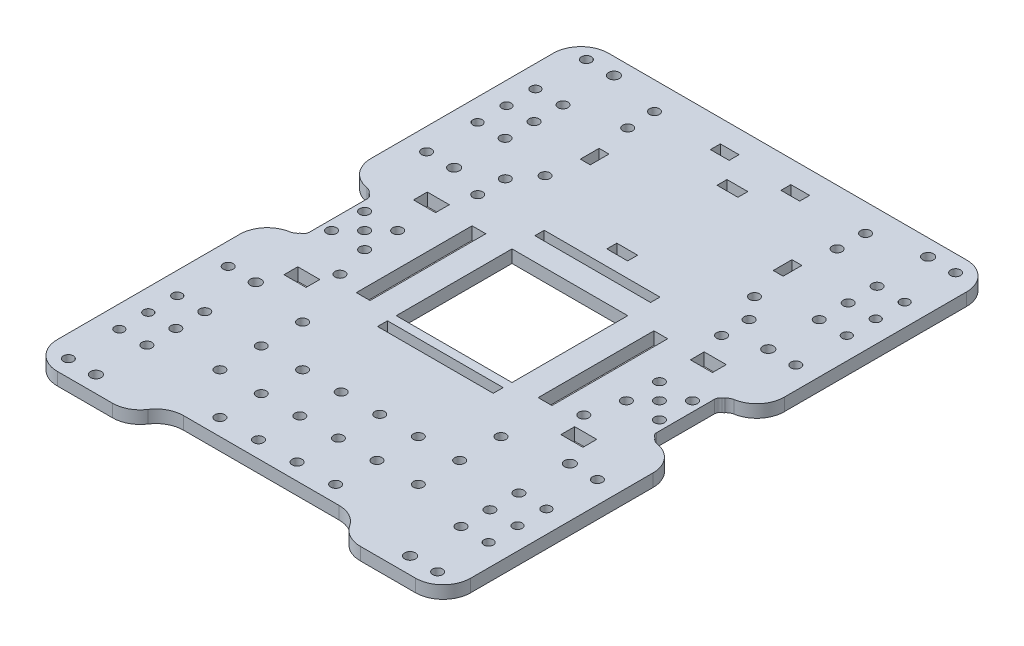
SolidWorks part; units mm, degrees
ref_plane "前视基准面" through (0, 0, 0) normal (0, 0, 1) x (1, 0, 0)
ref_plane "上视基准面" through (0, 0, 0) normal (0, 1, 0) x (1, 0, 0)
ref_plane "右视基准面" through (0, 0, 0) normal (1, 0, 0) x (0, 0, -1)
other "Configuration Table"
sketch "草图2" plane through (0, 0, 0) normal (0, 1, 0) x (1, 0, 0)
  line L0 (-65, 0) -> (65, 0) construction
  line L1 (-65, 100) -> (65, 100)
  line L2 (-65, 100) -> (-65, -100)
  line L3 (-65, -100) -> (65, -100)
  line L4 (65, 100) -> (65, -100)
  line L5 (-65, 100) -> (65, -100) construction
  line L6 (-65, -100) -> (65, 100) construction
  line L7 (65, 0) -> (63, 0) construction
  line L8 (63, 0) -> (59.5, 0) construction
  line L9 (59.5, 0) -> (47.5, 0) construction
  line L10 (47.5, 0) -> (53.5, 0) construction
  line L11 (53.5, 0) -> (53.5, 6) construction
  line L12 (53.5, 6) -> (53.5, -6) construction
  line L13 (53.5, -6) -> (47.5, -6) construction
  line L14 (47.5, -6) -> (47.5, 6) construction
  line L15 (47.5, 6) -> (59.5, 6) construction
  line L16 (59.5, 6) -> (59.5, -6) construction
  line L17 (-65, 0) -> (-63, 0) construction
  line L18 (-63, 0) -> (-59.5, 0) construction
  line L19 (-59.5, 0) -> (-47.5, 0) construction
  line L20 (-47.5, 0) -> (-53.5, 0) construction
  line L21 (-53.5, 0) -> (-53.5, 6) construction
  line L22 (-53.5, 6) -> (-53.5, -6) construction
  line L23 (-53.5, -6) -> (-59.5, -6) construction
  line L24 (-59.5, -6) -> (-59.5, 6) construction
  line L25 (-59.5, 6) -> (-47.5, 6) construction
  line L26 (-47.5, 6) -> (-47.5, -6) construction
  circle A0 centre (-59.5, 6) radius 1.8
  circle A1 centre (-47.5, 6) radius 1.8
  circle A2 centre (-59.5, -6) radius 1.8
  circle A3 centre (-47.5, -6) radius 1.8
  circle A4 centre (-53.5, 0) radius 1.8
  circle A5 centre (53.5, 0) radius 1.8
  circle A6 centre (59.5, 6) radius 1.8
  circle A7 centre (59.5, -6) radius 1.8
  circle A8 centre (47.5, -6) radius 1.8
  circle A9 centre (47.5, 6) radius 1.8
  point P0 (0, 0)
  dimension "D13" = 3.6
  dimension "D14" = 3.6
  dimension "D15" = 3.6
  dimension "D16" = 3.6
  dimension "D17" = 3.6
  dimension "D18" = 3.6
  dimension "D19" = 3.6
  dimension "D20" = 3.6
  dimension "D21" = 3.6
  dimension "D22" = 3.6
  dimension "D1" = 200
  dimension "D2" = 130
  dimension "D3" = 2
  dimension "D4" = 3.5
  dimension "D5" = 12
  dimension "D6" = 6
  dimension "D7" = 12
  dimension "D8" = 2
  dimension "D9" = 3.5
  dimension "D10" = 12
  dimension "D11" = 6
  dimension "D12" = 12
extrude "凸台-拉伸1" add sketch "草图2" along normal blind 4.6
fillet "圆角1" radius 5 4 edges at (-65, 2.3, -100) (65, 2.3, -100) (-65, 2.3, 100) (65, 2.3, 100)
sketch "草图3" plane through (0, 4.6, 0) normal (0, 1, 0) x (1, 0, 0)
  line L0 (-65, 0) -> (65, 0) construction
  line L1 (-65, 95) -> (-65, -95) construction
  line L2 (65, -95) -> (65, 95) construction
  line L4 (-63, 12) -> (-67, 12)
  line L5 (-63, 12) -> (-63, -12)
  line L6 (-63, -12) -> (-67, -12)
  line L7 (-67, 12) -> (-67, -12)
  line L8 (-63, 12) -> (-67, -12) construction
  line L9 (-63, -12) -> (-67, 12) construction
  line L10 (63, 12) -> (67, 12)
  line L11 (63, 12) -> (63, -12)
  line L12 (63, -12) -> (67, -12)
  line L13 (67, 12) -> (67, -12)
  line L14 (63, 12) -> (67, -12) construction
  line L15 (63, -12) -> (67, 12) construction
  dimension "D1" = 24
  dimension "D2" = 4
  dimension "D3" = 24
  dimension "D4" = 4
extrude "切除-拉伸1" cut sketch "草图3" against normal blind 4.6
fillet "圆角2" radius 2 4 edges at (65, 2.3, 12) (65, 2.3, -12) (-65, 2.3, 12) (-65, 2.3, -12)
fillet "圆角3" radius 2 4 edges at (-63, 2.3, 12) (-63, 2.3, -12) (63, 2.3, 12) (63, 2.3, -12)
sketch "草图4" plane through (0, 0, 0) normal (0, 1, 0) x (1, 0, 0)
  line L0 (65, 14) -> (57, 14) construction
  line L1 (57, 14) -> (57, 120) construction
  line L2 (65, -14) -> (57, -14) construction
  line L3 (65, -95) -> (65, -14) construction
  line L4 (57, -14) -> (57, -94) construction
  line L5 (57, -94) -> (57, -65) construction
  line L6 (57, -65) -> (57, -54) construction
  line L7 (-65, -94) -> (-57, -94) construction
  line L8 (-65, -14) -> (-65, -95) construction
  line L9 (-57, -94) -> (-57, -65) construction
  line L10 (-57, -65) -> (-57, -54.5) construction
  line L11 (-57, -54.5) -> (-57, -65) construction
  line L12 (-57, -65) -> (-57, -36) construction
  line L13 (57, -65) -> (57, -36) construction
  line L14 (57, 14) -> (57, 36) construction
  line L15 (57, 36) -> (57, 65) construction
  line L16 (57, 65) -> (57, 75.5) construction
  line L17 (57, 75.5) -> (57, 54.5) construction
  line L18 (57, 65) -> (57, 94) construction
  line L19 (-65, 14) -> (-57, 14) construction
  line L20 (-57, 14) -> (-57, 36) construction
  line L21 (-57, 36) -> (-57, 54.5) construction
  line L22 (-57, 54.5) -> (-57, 65) construction
  line L23 (-57, 65) -> (-57, 75.5) construction
  line L24 (-57, 75.5) -> (-57, 94) construction
  line L25 (-57, -65) -> (-57, -75.5) construction
  line L26 (-57, -75.5) -> (57, -75.5) construction
  line L27 (57, -65) -> (57, -54.5) construction
  arc A0 (65, -14) -> (64, -12.2679) centre (63, -14) ccw construction
  circle A1 centre (57, 65) radius 1.8
  circle A2 centre (57, 75.5) radius 1.8
  circle A3 centre (57, 54.5) radius 1.8
  circle A4 centre (57, 94) radius 1.95
  circle A5 centre (57, 36) radius 1.95
  circle A6 centre (-57, 94) radius 1.95
  circle A7 centre (-57, 75.5) radius 1.8
  circle A8 centre (-57, 65) radius 1.8
  circle A9 centre (-57, 54.5) radius 1.8
  circle A10 centre (-57, 36) radius 1.95
  circle A11 centre (-57, -36) radius 1.95
  circle A12 centre (-57, -65) radius 1.8
  circle A13 centre (-57, -54.5) radius 1.8
  circle A14 centre (-57, -75.5) radius 1.8
  circle A15 centre (-57, -94) radius 1.95
  circle A16 centre (57, -65) radius 1.8
  circle A18 centre (57, -75.5) radius 1.8
  circle A19 centre (57, -54.5) radius 1.8
  circle A20 centre (57, -36) radius 1.95
  circle A21 centre (57, -94) radius 1.95
  dimension "D15" = 3.6
  dimension "D16" = 3.6
  dimension "D17" = 3.6
  dimension "D18" = 3.9
  dimension "D19" = 3.9
  dimension "D20" = 3.9
  dimension "D21" = 3.6
  dimension "D22" = 3.6
  dimension "D23" = 3.6
  dimension "D24" = 3.9
  dimension "D25" = 3.9
  dimension "D26" = 3.6
  dimension "D27" = 3.6
  dimension "D29" = 3.6
  dimension "D30" = 3.9
  dimension "D31" = 3.6
  dimension "D32" = 10.5
  dimension "D33" = 3.6
  dimension "D34" = 3.6
  dimension "D35" = 3.9
  dimension "D36" = 3.9
  dimension "D1" = 8
  dimension "D2" = 106
  dimension "D3" = 8
  dimension "D4" = 80
  dimension "D5" = 29
  dimension "D6" = 11
  dimension "D7" = 8
  dimension "D8" = 29
  dimension "D9" = 22
  dimension "D10" = 29
  dimension "D11" = 10.5
  dimension "D12" = 21
  dimension "D13" = 29
  dimension "D14" = 8
  dimension "D28" = 10.5
extrude "切除-拉伸2" cut sketch "草图4" along normal blind 4.6
sketch "草图5" plane through (0, 4.6, 0) normal (0, 1, 0) x (1, 0, 0)
  line L0 (0, 100) -> (38.3, 100) construction
  line L1 (60, 100) -> (-60, 100) construction
  line L2 (38.3, 100) -> (-38.3, 100) construction
  line L3 (-38.3, 100) -> (-38.3, 90) construction
  line L4 (-38.3, 90) -> (-12.8, 90) construction
  line L5 (38.3, 100) -> (38.3, 90) construction
  line L6 (38.3, 90) -> (12.8, 90) construction
  line L7 (0, 21) -> (0, 31) construction
  line L8 (-16.2, 91.8) -> (-9.4, 91.8)
  line L9 (-16.2, 91.8) -> (-16.2, 88.2)
  line L10 (-16.2, 88.2) -> (-9.4, 88.2)
  line L11 (-9.4, 91.8) -> (-9.4, 88.2)
  line L12 (-16.2, 91.8) -> (-9.4, 88.2) construction
  line L13 (-16.2, 88.2) -> (-9.4, 91.8) construction
  line L14 (9.4, 91.8) -> (16.2, 91.8)
  line L15 (9.4, 91.8) -> (9.4, 88.2)
  line L16 (9.4, 88.2) -> (16.2, 88.2)
  line L17 (16.2, 91.8) -> (16.2, 88.2)
  line L18 (9.4, 91.8) -> (16.2, 88.2) construction
  line L19 (9.4, 88.2) -> (16.2, 91.8) construction
  line L20 (-21, 21) -> (21, 21)
  line L21 (-21, 21) -> (-21, -21)
  line L22 (-21, -21) -> (21, -21)
  line L23 (21, 21) -> (21, -21)
  line L24 (-21, 21) -> (21, -21) construction
  line L25 (-21, -21) -> (21, 21) construction
  line L26 (0, 31) -> (0, -21) construction
  line L27 (0, -21) -> (0, -31) construction
  line L28 (-60, -100) -> (60, -100) construction
  line L29 (-21, 32.7) -> (21, 32.7)
  line L30 (-21, 32.7) -> (-21, 29.3)
  line L31 (-21, 29.3) -> (21, 29.3)
  line L32 (21, 32.7) -> (21, 29.3)
  line L33 (-21, 32.7) -> (21, 29.3) construction
  line L34 (-21, 29.3) -> (21, 32.7) construction
  line L35 (-21, -29.3) -> (21, -29.3)
  line L36 (-21, -29.3) -> (-21, -32.7)
  line L37 (-21, -32.7) -> (21, -32.7)
  line L38 (21, -29.3) -> (21, -32.7)
  line L39 (-21, -29.3) -> (21, -32.7) construction
  line L40 (-21, -32.7) -> (21, -29.3) construction
  line L41 (-35, -91) -> (35, -91)
  line L42 (-35, -91) -> (-35, -109)
  line L43 (-35, -109) -> (35, -109)
  line L44 (35, -91) -> (35, -109)
  line L45 (-35, -91) -> (35, -109) construction
  line L46 (-35, -109) -> (35, -91) construction
  circle A0 centre (38.3, 90) radius 1.8
  circle A1 centre (-38.3, 90) radius 1.8
  point P19 (0, 0)
  point P37 (0, -100)
  dimension "D7" = 3.6
  dimension "D8" = 3.6
  dimension "D1" = 38.3
  dimension "D2" = 76.6
  dimension "D3" = 10
  dimension "D4" = 25.5
  dimension "D5" = 10
  dimension "D6" = 25.5
  dimension "D9" = 3.6
  dimension "D10" = 6.8
  dimension "D11" = 3.6
  dimension "D12" = 6.8
  dimension "D13" = 42
  dimension "D14" = 10
  dimension "D15" = 10
  dimension "D16" = 3.4
  dimension "D17" = 42
  dimension "D18" = 3.4
  dimension "D19" = 42
  dimension "D20" = 18
  dimension "D21" = 70
extrude "切除-拉伸3" cut sketch "草图5" against normal blind 4.6
fillet "圆角4" radius 10 2 edges at (-35, 2.3, 100) (35, 2.3, 100)
fillet "圆角5" radius 10 2 edges at (-35, 2.3, 91) (35, 2.3, 91)
sketch "草图6" plane through (0, 4.6, 0) normal (0, 1, 0) x (1, 0, 0)
  line L0 (0, -91) -> (0, -85) construction
  line L1 (28.2466, -91) -> (-28.2466, -91) construction
  line L2 (0, -85) -> (-7, -85) construction
  line L3 (-7, -85) -> (7, -85) construction
  line L4 (7, -85) -> (21, -85) construction
  line L5 (21, -85) -> (21, -70) construction
  line L6 (21, -70) -> (21, -55) construction
  line L7 (21, -55) -> (7, -55) construction
  line L8 (7, -55) -> (-7, -55) construction
  line L9 (-7, -55) -> (-21, -55) construction
  line L10 (-21, -55) -> (-35, -55) construction
  line L11 (-35, -55) -> (-35, -70) construction
  line L12 (-35, -70) -> (-35, -85) construction
  line L13 (-35, -85) -> (-21, -85) construction
  line L14 (21, -85) -> (35, -85) construction
  line L15 (35, -85) -> (35, -70) construction
  line L16 (35, -70) -> (35, -55) construction
  line L17 (35, -55) -> (35, -40) construction
  line L18 (35, -40) -> (21, -40) construction
  line L19 (21, -40) -> (7, -40) construction
  line L20 (7, -40) -> (-7, -40) construction
  line L21 (-7, -40) -> (-21, -40) construction
  line L22 (-21, -40) -> (-35, -40) construction
  line L23 (-35, -40) -> (-35, -70) construction
  line L24 (-35, -70) -> (-21, -70) construction
  line L25 (-21, -70) -> (-7, -70) construction
  line L26 (-7, -70) -> (7, -70) construction
  line L27 (21, -70) -> (36, -70) construction
  line L28 (36, -70) -> (36, -55) construction
  line L29 (36, -55) -> (36, -40) construction
  line L30 (-21, -70) -> (-36, -70) construction
  line L31 (-36, -70) -> (-36, -55) construction
  line L32 (-36, -55) -> (-36, -40) construction
  circle A0 centre (-7, -85) radius 1.8
  circle A1 centre (-21, -85) radius 1.8
  circle A2 centre (7, -85) radius 1.8
  circle A3 centre (21, -85) radius 1.8
  circle A4 centre (21, -70) radius 1.8
  circle A5 centre (7, -70) radius 1.8
  circle A6 centre (-7, -70) radius 1.8
  circle A7 centre (-21, -70) radius 1.8
  circle A8 centre (-21, -55) radius 1.8
  circle A9 centre (-7, -55) radius 1.8
  circle A10 centre (7, -55) radius 1.8
  circle A11 centre (21, -55) radius 1.8
  circle A12 centre (36, -70) radius 1.8
  circle A13 centre (36, -55) radius 1.8
  circle A14 centre (36, -40) radius 1.8
  circle A15 centre (-36, -40) radius 1.8
  circle A16 centre (-36, -55) radius 1.8
  circle A17 centre (-36, -70) radius 1.8
  dimension "D15" = 3.6
  dimension "D16" = 3.6
  dimension "D17" = 3.6
  dimension "D18" = 3.6
  dimension "D19" = 3.6
  dimension "D20" = 3.6
  dimension "D21" = 3.6
  dimension "D22" = 3.6
  dimension "D23" = 3.6
  dimension "D24" = 3.6
  dimension "D25" = 3.6
  dimension "D26" = 3.6
  dimension "D27" = 15
  dimension "D33" = 3.6
  dimension "D34" = 3.6
  dimension "D35" = 3.6
  dimension "D36" = 3.6
  dimension "D37" = 3.6
  dimension "D38" = 3.6
  dimension "D1" = 6
  dimension "D2" = 7
  dimension "D3" = 14
  dimension "D4" = 14
  dimension "D5" = 15
  dimension "D6" = 15
  dimension "D7" = 14
  dimension "D8" = 14
  dimension "D9" = 14
  dimension "D10" = 14
  dimension "D11" = 15
  dimension "D12" = 14
  dimension "D13" = 14
  dimension "D14" = 15
  dimension "D28" = 15
  dimension "D29" = 15
  dimension "D30" = 15
  dimension "D31" = 15
  dimension "D32" = 15
extrude "切除-拉伸4" cut sketch "草图6" against normal blind 4.6
sketch "草图7" plane through (0, 4.6, 0) normal (0, 1, 0) x (1, 0, 0)
  line L0 (0, 100) -> (38, 100) construction
  line L1 (60, 100) -> (-60, 100) construction
  line L2 (38, 100) -> (-38, 100) construction
  line L3 (-38, 100) -> (-38, 80) construction
  line L4 (-38, 80) -> (-38, 50) construction
  line L5 (-38, 50) -> (38, 50) construction
  line L6 (38, 50) -> (38, 80) construction
  circle A0 centre (-38, 80) radius 1.8
  circle A1 centre (38, 80) radius 1.8
  circle A2 centre (38, 50) radius 1.8
  circle A3 centre (-38, 50) radius 1.8
  dimension "D7" = 3.6
  dimension "D8" = 3.6
  dimension "D9" = 3.6
  dimension "D10" = 3.6
  dimension "D1" = 38
  dimension "D2" = 76
  dimension "D3" = 20
  dimension "D4" = 30
  dimension "D5" = 76
  dimension "D6" = 30
extrude "切除-拉伸5" cut sketch "草图7" against normal blind 4.6
sketch "草图8" plane through (0, 4.6, 0) normal (0, 1, 0) x (1, 0, 0)
  line L0 (-38, 80) -> (38, 50) construction
  line L1 (38, 50) -> (0, 65) construction
  line L2 (0, 65) -> (-35, 65) construction
  line L3 (-35, 65) -> (35, 65) construction
  line L4 (35, 65) -> (0, 65) construction
  line L5 (0, 65) -> (0, 80) construction
  line L6 (0, 80) -> (0, 40) construction
  line L8 (-3.7805, 81.7985) -> (3.7805, 81.7985)
  line L9 (-3.7805, 81.7985) -> (-3.7805, 78.2015)
  line L10 (-3.7805, 78.2015) -> (3.7805, 78.2015)
  line L11 (3.7805, 81.7985) -> (3.7805, 78.2015)
  line L12 (-3.7805, 81.7985) -> (3.7805, 78.2015) construction
  line L13 (-3.7805, 78.2015) -> (3.7805, 81.7985) construction
  line L14 (-3.7805, 38.1892) -> (3.7805, 38.1892)
  line L15 (-3.7805, 38.1892) -> (-3.7805, 41.8108)
  line L16 (-3.7805, 41.8108) -> (3.7805, 41.8108)
  line L17 (3.7805, 38.1892) -> (3.7805, 41.8108)
  line L18 (-3.7805, 38.1892) -> (3.7805, 41.8108) construction
  line L19 (-3.7805, 41.8108) -> (3.7805, 38.1892) construction
  line L20 (33.2, 68.4) -> (36.8, 68.4)
  line L21 (33.2, 68.4) -> (33.2, 61.6)
  line L22 (33.2, 61.6) -> (36.8, 61.6)
  line L23 (36.8, 68.4) -> (36.8, 61.6)
  line L24 (33.2, 68.4) -> (36.8, 61.6) construction
  line L25 (33.2, 61.6) -> (36.8, 68.4) construction
  line L26 (-36.8, 68.4) -> (-33.2, 68.4)
  line L27 (-36.8, 68.4) -> (-36.8, 61.6)
  line L28 (-36.8, 61.6) -> (-33.2, 61.6)
  line L29 (-33.2, 68.4) -> (-33.2, 61.6)
  line L30 (-36.8, 68.4) -> (-33.2, 61.6) construction
  line L31 (-36.8, 61.6) -> (-33.2, 68.4) construction
  dimension "D1" = 35
  dimension "D2" = 70
  dimension "D3" = 40
  dimension "D4" = 6.8
  dimension "D5" = 3.6
  dimension "D6" = 6.8
  dimension "D7" = 3.6
extrude "切除-拉伸6" cut sketch "草图8" against normal blind 4.6
sketch "草图10" plane through (0, 4.6, 0) normal (0, 1, 0) x (1, 0, 0)
  line L0 (0, 0) -> (44.25, 0) construction
  line L1 (44.25, 0) -> (-44.25, 0) construction
  line L2 (36, -38.2) -> (73.5514, -38.2) construction
  line L3 (73.5514, -38.2) -> (-76.1567, -38.2) construction
  line L4 (44.25, 0) -> (44.25, -38.2) construction
  line L5 (44.25, -38.2) -> (44.25, -18.2) construction
  line L6 (-44.25, 0) -> (-44.25, -38.2) construction
  line L7 (-44.25, -38.2) -> (-44.25, -18.1899) construction
  line L8 (-44.25, -18.1899) -> (-43.1477, 41.8) construction
  line L9 (-43.1477, 41.8) -> (44.25, 41.8) construction
  line L10 (0, 38.1892) -> (-44.25, 38.1892) construction
  line L11 (-3.7805, 38.1892) -> (3.7805, 38.1892) construction
  line L12 (-44.25, 38.1892) -> (44.25, 38.1892) construction
  line L13 (-44.25, -18.1899) -> (-44.25, 41.8101) construction
  line L14 (44.25, -18.2) -> (44.25, 41.8) construction
  line L15 (44.25, -18.2) -> (44.25, -8.2) construction
  line L16 (-44.25, -18.1899) -> (-44.25, -8.1899) construction
  line L17 (-44.25, -18.1899) -> (-44.25, 31.8101) construction
  line L18 (-44.25, 31.8101) -> (44.25, 31.8101) construction
  circle A0 centre (36, -40) radius 1.8 construction
  circle A1 centre (44.25, 41.8) radius 1.8
  circle A2 centre (-44.25, 41.8101) radius 1.8
  circle A3 centre (-44.25, -18.1899) radius 1.8
  circle A4 centre (44.25, -18.2) radius 1.8
  circle A5 centre (-44.25, 31.8101) radius 1.8
  circle A6 centre (44.25, 31.8101) radius 1.8
  dimension "D9" = 3.6
  dimension "D10" = 3.6
  dimension "D11" = 3.6
  dimension "D12" = 3.6
  dimension "D16" = 3.6
  dimension "D17" = 3.6
  dimension "D1" = 44.25
  dimension "D2" = 88.5
  dimension "D3" = 20
  dimension "D4" = 60
  dimension "D5" = 44.25
  dimension "D6" = 88.5
  dimension "D7" = 60
  dimension "D8" = 60
  dimension "D13" = 10
  dimension "D14" = 10
  dimension "D15" = 50
extrude "切除-拉伸8" cut sketch "草图10" against normal blind 4.6
sketch "草图9" plane through (0, 4.6, 0) normal (0, 1, 0) x (1, 0, 0)
  line L0 (21, 0) -> (33, 0) construction
  line L1 (21, -21) -> (21, 21) construction
  line L2 (-21, 0) -> (-33, 0) construction
  line L3 (-21, 21) -> (-21, -21) construction
  line L4 (35.5, -21) -> (65, -21) construction
  line L9 (30.5, 21) -> (35.5, -21) construction
  line L10 (30.5, -21) -> (35.5, 21) construction
  line L15 (-35.5, 21) -> (-30.5, -21) construction
  line L16 (-35.5, -21) -> (-30.5, 21) construction
  line L17 (65, -95) -> (65, -14) construction
  line L18 (-35.5, -21) -> (-65, -21) construction
  line L23 (46.25, -18.5) -> (54.25, -23.5) construction
  line L24 (46.25, -23.5) -> (54.25, -18.5) construction
  line L25 (-65, -14) -> (-65, -95) construction
  line L26 (-35.5, 21) -> (-65, 21) construction
  line L31 (-54.25, -18.5) -> (-46.25, -23.5) construction
  line L32 (-54.25, -23.5) -> (-46.25, -18.5) construction
  line L33 (-65, 95) -> (-65, 14) construction
  line L34 (35.5, 21) -> (65, 21) construction
  line L35 (-54.25, 23.5) -> (-46.25, 23.5)
  line L36 (-54.25, 23.5) -> (-54.25, 18.5)
  line L37 (-54.25, 18.5) -> (-46.25, 18.5)
  line L38 (-46.25, 23.5) -> (-46.25, 18.5)
  line L39 (-54.25, 23.5) -> (-46.25, 18.5) construction
  line L40 (-54.25, 18.5) -> (-46.25, 23.5) construction
  line L41 (65, 14) -> (65, 95) construction
  line L42 (50.25, -21) -> (50.25, -31) construction
  line L43 (46.25, 23.5) -> (54.25, 23.5)
  line L44 (46.25, 23.5) -> (46.25, 18.5)
  line L45 (46.25, 18.5) -> (54.25, 18.5)
  line L46 (54.25, 23.5) -> (54.25, 18.5)
  line L47 (46.25, 23.5) -> (54.25, 18.5) construction
  line L48 (46.25, 18.5) -> (54.25, 23.5) construction
  line L49 (50.25, -31) -> (50.25, -26) construction
  line L50 (50.25, -26) -> (-50.25, -26) construction
  line L52 (-54.25, -23.5) -> (-46.25, -23.5)
  line L53 (-54.25, -23.5) -> (-54.25, -28.5)
  line L54 (-54.25, -28.5) -> (-46.25, -28.5)
  line L55 (-46.25, -23.5) -> (-46.25, -28.5)
  line L56 (-54.25, -23.5) -> (-46.25, -28.5) construction
  line L57 (-54.25, -28.5) -> (-46.25, -23.5) construction
  line L58 (46.25, -23.5) -> (54.25, -23.5)
  line L59 (46.25, -23.5) -> (46.25, -28.5)
  line L60 (46.25, -28.5) -> (54.25, -28.5)
  line L61 (54.25, -23.5) -> (54.25, -28.5)
  line L62 (46.25, -23.5) -> (54.25, -28.5) construction
  line L63 (46.25, -28.5) -> (54.25, -23.5) construction
  line L64 (30.5, 21) -> (35.5, 21)
  line L65 (30.5, 21) -> (30.5, -21)
  line L66 (30.5, -21) -> (35.5, -21)
  line L67 (35.5, 21) -> (35.5, -21)
  line L68 (30.5, 21) -> (35.5, -21) construction
  line L69 (30.5, -21) -> (35.5, 21) construction
  line L70 (-35.5, 21) -> (-30.5, 21)
  line L71 (-35.5, 21) -> (-35.5, -21)
  line L72 (-35.5, -21) -> (-30.5, -21)
  line L73 (-30.5, 21) -> (-30.5, -21)
  line L74 (-35.5, 21) -> (-30.5, -21) construction
  line L75 (-35.5, -21) -> (-30.5, 21) construction
  point P17 (50.25, -21)
  point P25 (-50.25, -21)
  point P33 (-50.25, 21)
  point P41 (50.25, 21)
  dimension "D1" = 12
  dimension "D2" = 12
  dimension "D3" = 42
  dimension "D4" = 5
  dimension "D5" = 42
  dimension "D6" = 5
  dimension "D7" = 5
  dimension "D8" = 8
  dimension "D9" = 5
  dimension "D10" = 8
  dimension "D11" = 5
  dimension "D12" = 8
  dimension "D13" = 5
  dimension "D14" = 8
  dimension "D15" = 10
  dimension "D16" = 5
  dimension "D17" = 8
  dimension "D18" = 5
  dimension "D19" = 8
extrude "切除-拉伸9" cut sketch "草图9" against normal blind 4.6
sketch "草图12" plane through (0, 0, 0) normal (0, -1, 0) x (1, 0, 0)
  line L0 (-46.25, 28.5) -> (-46.25, 23.5) construction
  line L1 (-65, 100) -> (-46.25, 100)
  line L2 (-65, 100) -> (-65, 28.5)
  line L3 (-65, 28.5) -> (-46.25, 28.5)
  line L4 (-46.25, 100) -> (-46.25, 28.5)
  line L5 (-54.25, 28.5) -> (-46.25, 28.5) construction
  line L6 (65, 95) -> (65, 100.0021) construction
  line L7 (-60, -100) -> (-65, -100) construction
  line L8 (65, 100.0021) -> (46.25, 100.0021)
  line L9 (65, 100.0021) -> (65, 28.5)
  line L10 (65, 28.5) -> (46.25, 28.5)
  line L11 (46.25, 100.0021) -> (46.25, 28.5)
  line L12 (-46.25, -23.5) -> (-54.25, -23.5) construction
  line L13 (-65, -100) -> (-50.25, -100)
  line L14 (-65, -100) -> (-65, -23.5)
  line L15 (-65, -23.5) -> (-50.25, -23.5)
  line L16 (-50.25, -100) -> (-50.25, -23.5)
  line L17 (54.25, -23.5) -> (46.25, -23.5) construction
  line L18 (65, -99.9979) -> (50.25, -99.9979)
  line L19 (65, -99.9979) -> (65, -23.5)
  line L20 (65, -23.5) -> (50.25, -23.5)
  line L21 (50.25, -99.9979) -> (50.25, -23.5)
  line L22 (-50.25, -55.9334) -> (50.25, -55.9334) construction
  line L23 (50.25, -55.9334) -> (50.25, -72.845) construction
  line L24 (50.25, -72.845) -> (-50.25, -72.845) construction
  line L25 (-21, 85) -> (-21, 70) construction
  line L26 (-21, 70) -> (-21, 77.5) construction
  line L27 (-21, 77.5) -> (-46.25, 77.5) construction
  line L28 (-46.25, 77.5) -> (46.25, 77.5) construction
  line L29 (46.25, 77.5) -> (0, 77.5) construction
  line L30 (0, 77.5) -> (0, 62.5) construction
  line L31 (0, 62.5) -> (0, 47.5) construction
  line L32 (0, 77.5) -> (0, 92.5) construction
  line L33 (-28.2466, 91) -> (-46.25, 91) construction
  line L34 (-46.25, 91) -> (46.25, 91) construction
  line L35 (-21, 32.7) -> (-46.25, 32.7) construction
  line L36 (-46.25, 79.5003) -> (46.25, 79.5003)
  line L37 (-46.25, 79.5003) -> (-46.25, 75.4997)
  line L38 (-46.25, 75.4997) -> (46.25, 75.4997)
  line L39 (46.25, 79.5003) -> (46.25, 75.4997)
  line L40 (-46.25, 79.5003) -> (46.25, 75.4997) construction
  line L41 (-46.25, 75.4997) -> (46.25, 79.5003) construction
  line L42 (-46.25, 64.5) -> (46.25, 64.5)
  line L43 (-46.25, 64.5) -> (-46.25, 60.5)
  line L44 (-46.25, 60.5) -> (46.25, 60.5)
  line L45 (46.25, 64.5) -> (46.25, 60.5)
  line L46 (-46.25, 64.5) -> (46.25, 60.5) construction
  line L47 (-46.25, 60.5) -> (46.25, 64.5) construction
  line L48 (-46.25, 49.5) -> (46.25, 49.5)
  line L49 (-46.25, 49.5) -> (-46.25, 45.5)
  line L50 (-46.25, 45.5) -> (46.25, 45.5)
  line L51 (46.25, 49.5) -> (46.25, 45.5)
  line L52 (-46.25, 49.5) -> (46.25, 45.5) construction
  line L53 (-46.25, 45.5) -> (46.25, 49.5) construction
  line L54 (-46.25, 91) -> (46.25, 91)
  line L55 (-46.25, 91) -> (-46.25, 89)
  line L56 (-46.25, 89) -> (46.25, 89)
  line L57 (46.25, 91) -> (46.25, 89)
  line L58 (-46.25, 32.7) -> (46.25, 32.7) construction
  line L59 (0, -55.9334) -> (0, -57.8166) construction
  line L60 (-46.25, 32.7) -> (46.25, 32.7)
  line L61 (-46.25, 32.7) -> (-46.25, 34.7)
  line L62 (-46.25, 34.7) -> (46.25, 34.7)
  line L63 (46.25, 32.7) -> (46.25, 34.7)
  line L64 (-38, -81.8) -> (-38, -88.2252) construction
  line L65 (-50.25, -54.875) -> (50.25, -54.875)
  line L66 (-50.25, -54.875) -> (-50.25, -58.875)
  line L67 (-50.25, -58.875) -> (50.25, -58.875)
  line L68 (50.25, -54.875) -> (50.25, -58.875)
  line L69 (-50.25, -54.875) -> (50.25, -58.875) construction
  line L70 (-50.25, -58.875) -> (50.25, -54.875) construction
  line L71 (-50.25, -74.845) -> (50.25, -74.845)
  line L72 (-50.25, -74.845) -> (-50.25, -70.845)
  line L73 (-50.25, -70.845) -> (50.25, -70.845)
  line L74 (50.25, -74.845) -> (50.25, -70.845)
  line L75 (-50.25, -74.845) -> (50.25, -70.845) construction
  line L76 (-50.25, -70.845) -> (50.25, -74.845) construction
  line L77 (-38, -85.0126) -> (67.8048, -85.0126) construction
  line L78 (0, -81.7985) -> (0, -85.0126) construction
  line L79 (3.7805, -81.7985) -> (-3.7805, -81.7985) construction
  line L80 (0, -85.0126) -> (0, -95.8032) construction
  line L81 (-50.25, -84.0126) -> (50.25, -84.0126)
  line L82 (-50.25, -84.0126) -> (-50.25, -86.0126)
  line L83 (-50.25, -86.0126) -> (50.25, -86.0126)
  line L84 (50.25, -84.0126) -> (50.25, -86.0126)
  line L85 (-50.25, -84.0126) -> (50.25, -86.0126) construction
  line L86 (-50.25, -86.0126) -> (50.25, -84.0126) construction
  line L87 (0, -56.875) -> (0, -72.845) construction
  line L88 (-50.25, -94.3032) -> (50.25, -94.3032)
  line L89 (-50.25, -94.3032) -> (-50.25, -97.3032)
  line L90 (-50.25, -97.3032) -> (50.25, -97.3032)
  line L91 (50.25, -94.3032) -> (50.25, -97.3032)
  line L92 (-50.25, -94.3032) -> (50.25, -97.3032) construction
  line L93 (-50.25, -97.3032) -> (50.25, -94.3032) construction
  line L94 (3.7805, -80) -> (36.2, -80) construction
  line L95 (-2, -58.875) -> (2, -58.875)
  line L96 (-2, -58.875) -> (-2, -70.845)
  line L97 (-2, -70.845) -> (2, -70.845)
  line L98 (2, -58.875) -> (2, -70.845)
  line L99 (-2, -58.875) -> (2, -70.845) construction
  line L100 (-2, -70.845) -> (2, -58.875) construction
  line L101 (3.7805, -78.2015) -> (3.7805, -81.7985) construction
  line L102 (-3.7805, -80) -> (-36.2, -80) construction
  line L103 (-3.7805, -81.7985) -> (-3.7805, -78.2015) construction
  line L104 (22.8, 55) -> (34.2, 55) construction
  line L105 (17.9902, -85.155) -> (21.9902, -85.155)
  line L106 (17.9902, -85.155) -> (17.9902, -74.845)
  line L107 (17.9902, -74.845) -> (21.9902, -74.845)
  line L108 (21.9902, -85.155) -> (21.9902, -74.845)
  line L109 (17.9902, -85.155) -> (21.9902, -74.845) construction
  line L110 (17.9902, -74.845) -> (21.9902, -85.155) construction
  line L111 (-21.9902, -85.845) -> (-17.9902, -85.845)
  line L112 (-21.9902, -85.845) -> (-21.9902, -74.155)
  line L113 (-21.9902, -74.155) -> (-17.9902, -74.155)
  line L114 (-17.9902, -85.845) -> (-17.9902, -74.155)
  line L115 (-21.9902, -85.845) -> (-17.9902, -74.155) construction
  line L116 (-21.9902, -74.155) -> (-17.9902, -85.845) construction
  line L117 (-2, -84.9529) -> (2, -84.9529)
  line L118 (-2, -84.9529) -> (-2, -95.8629)
  line L119 (-2, -95.8629) -> (2, -95.8629)
  line L120 (2, -84.9529) -> (2, -95.8629)
  line L121 (-2, -84.9529) -> (2, -95.8629) construction
  line L122 (-2, -95.8629) -> (2, -84.9529) construction
  line L123 (-2, 49) -> (2, 49)
  line L124 (-2, 49) -> (-2, 91)
  line L125 (-2, 91) -> (2, 91)
  line L126 (2, 49) -> (2, 91)
  line L127 (-2, 49) -> (2, 91) construction
  line L128 (-2, 91) -> (2, 49) construction
  line L129 (-34.2, 55) -> (-22.8, 55) construction
  line L131 (26.5, 75.3) -> (30.5, 75.3)
  line L132 (26.5, 75.3) -> (26.5, 34.7)
  line L133 (26.5, 34.7) -> (30.5, 34.7)
  line L134 (30.5, 75.3) -> (30.5, 34.7)
  line L135 (26.5, 75.3) -> (30.5, 34.7) construction
  line L136 (26.5, 34.7) -> (30.5, 75.3) construction
  line L137 (-30.5, 75.3) -> (-26.5, 75.3)
  line L138 (-30.5, 75.3) -> (-30.5, 34.7)
  line L139 (-30.5, 34.7) -> (-26.5, 34.7)
  line L140 (-26.5, 75.3) -> (-26.5, 34.7)
  line L141 (-30.5, 75.3) -> (-26.5, 34.7) construction
  line L142 (-30.5, 34.7) -> (-26.5, 75.3) construction
  circle A0 centre (-57, 94) radius 1.95
  circle A1 centre (-57, 75.5) radius 1.8
  circle A2 centre (-57, 65) radius 1.8143
  circle A3 centre (-57, 54.5) radius 1.8
  circle A4 centre (-57, 36) radius 1.95
  circle A5 centre (57, 94) radius 1.95
  circle A6 centre (57, 75.5) radius 1.8
  circle A7 centre (57, 65) radius 1.8
  circle A8 centre (57, 54.5) radius 1.8
  circle A9 centre (57, 36) radius 1.95
  circle A10 centre (57, -36) radius 1.95
  circle A11 centre (57, -54.5) radius 1.8
  circle A12 centre (57, -65) radius 1.8
  circle A13 centre (57, -75.5) radius 1.8
  circle A14 centre (57, -94) radius 1.95
  circle A15 centre (-57, -94) radius 1.95
  circle A16 centre (-57, -75.5) radius 1.8
  circle A17 centre (-57, -65) radius 1.8
  circle A18 centre (-57, -54.5) radius 1.8
  circle A19 centre (-57, -36) radius 1.95
  circle A20 centre (-38, -80) radius 1.8 construction
  circle A21 centre (-38.3, -90) radius 1.8 construction
  circle A22 centre (38, -80) radius 1.8 construction
  circle A23 centre (21, 55) radius 1.8 construction
  circle A24 centre (36, 55) radius 1.8 construction
  circle A25 centre (-36, 55) radius 1.8 construction
  circle A26 centre (-21, 55) radius 1.8 construction
  point P133 (0, -56.875)
  point P138 (0, -72.845)
  point P167 (0, -64.86)
  point P183 (19.9902, -80)
  point P188 (-19.9902, -80)
  point P193 (0, -90.4079)
  point P198 (0, 70)
  point P217 (28.5, 55)
  point P222 (-28.5, 55)
  dimension "D1" = 15
  dimension "D2" = 15
  dimension "D3" = 15
  dimension "D4" = 4.0007
  dimension "D5" = 92.5
  dimension "D6" = 4
  dimension "D7" = 4
  dimension "D8" = 2
  dimension "D9" = 2
  dimension "D10" = 4
  dimension "D11" = 4
  dimension "D12" = 2
  dimension "D13" = 3
  dimension "D14" = 11.97
  dimension "D15" = 4
  dimension "D16" = 10.31
  dimension "D17" = 4
  dimension "D18" = 11.69
  dimension "D19" = 4
  dimension "D20" = 10.91
  dimension "D21" = 4
  dimension "D22" = 42
  dimension "D23" = 4
  dimension "D24" = 40.6
  dimension "D25" = 4
  dimension "D26" = 40.6
  dimension "D27" = 4
extrude "凸台-拉伸2" add sketch "草图12" along normal blind 2 contours L4 L1 L2 L3 A4 A3 A2 A1 A0 | L56 L126 L54 L124 | L126 L56 L11 L54 | L56 L124 L54 L4 | L36 L126 L56 L124 | L8 L11 L10 L9 A9 A8 A7 A6 A5 | L126 L38 L11 L36 | L38 L126 L36 L124 | L38 L124 L36 L4 | L42 L126 L38 L124 | L134 L131 L132 L42 | L140 L137 L138 L42 | L138 L42 L4 L44 | L140 L42 L138 L44 | L42 L140 L44 L124 | L44 L126 L42 L124 | L132 L42 L126 L44 | L134 L42 L132 L44 | L42 L134 L44 L11 | L134 L44 L132 L48 | L48 L134 L50 L11 | L134 L50 L132 L62 | L62 L4 L60 L11 | L134 L48 L132 L50 | L48 L140 L50 L132 L126 L123 L124 | L48 L126 L44 L124 | L123 L126 L48 L124 | L140 L44 L138 L48 | L138 L48 L4 L50 | L140 L48 L138 L50 | L140 L50 L138 L62 | L21 L18 L19 L20 A14 A13 A12 A11 A10 | L13 L16 L15 L14 A19 A18 A17 A16 A15 | L16 L67 L21 L65 | L98 L67 L96 L73 | L114 L71 L21 L73 L16 L112 L113 | L81 L108 L71 L106 | L81 L114 L71 L112 | L71 L114 L113 L112 | L117 L120 L83 L21 L81 L108 L105 L106 L114 L111 L112 L16 L118 | L111 L114 L81 L112 | L105 L108 L81 L106 | L120 L117 L118 L83 | L120 L83 L118 L88 | L88 L120 L119 L118 L16 L90 L21 | L120 L88 L118 L119 region at (-55.625, 0, 99.2608) region at (-24.125, 0, 90) region at (0, 0, 90) region at (0, 0, 33.7) region at (-24.125, 0, 77.5) region at (0, 0, 84.2502) region at (24.125, 0, 90) region at (46.9892, 0, 33.7) region at (0, 0, 77.5) region at (-38.375, 0, 47.5) region at (-28.5, 0, 40.1) region at (-38.375, 0, 62.5) region at (0, 0, 69.9998) region at (24.125, 0, 77.5) region at (-28.5, 0, 47.5) region at (38.375, 0, 47.5) region at (28.5, 0, 40.1) region at (-28.5, 0, 69.9) region at (-28.5, 0, 62.5) region at (-14.25, 0, 62.5) region at (0, 0, 62.5) region at (-28.5, 0, 55) region at (0, 0, 47.4833) region at (28.5, 0, 47.5) region at (14.25, 0, 62.5) region at (0, 0, 55) region at (38.375, 0, 62.5) region at (28.5, 0, 55) region at (28.5, 0, 69.9) region at (28.5, 0, 62.5) region at (0, 0, 49.25) region at (-57.6567, 0, -61.5853) region at (-49.2446, 0, -95.8032) region at (57.6567, 0, -61.5842) region at (0, 0, -56.875) region at (-49.2448, 0, -85.0126) region at (0, 0, -90.1579) region at (0, 0, -95.083) region at (0, 0, -85.4827) region at (0.1382, 0, -72.8336) region at (0, 0, -64.86) region at (-19.9902, 0, -79.4288) region at (-19.9902, 0, -84.9288) region at (-19.9902, 0, -74.5) region at (19.9902, 0, -84.5838) region at (19.9902, 0, -79.4288)
sketch "草图13" plane through (0, 0, 0) normal (0, -1, 0) x (1, 0, 0)
  line L0 (0, -41.8108) -> (0, -45.8108) construction
  line L1 (3.7805, -41.8108) -> (-3.7805, -41.8108) construction
  line L3 (-15, -45.8108) -> (15, -45.8108)
  line L4 (-15, -45.8108) -> (-15, -41.8108)
  line L5 (-15, -41.8108) -> (15, -41.8108)
  line L6 (15, -45.8108) -> (15, -41.8108)
  line L7 (-15, -45.8108) -> (15, -41.8108) construction
  line L8 (-15, -41.8108) -> (15, -45.8108) construction
  point P5 (0, -43.8108)
  dimension "D1" = 4
  dimension "D2" = 4
  dimension "D3" = 30
extrude "凸台-拉伸3" add sketch "草图13" along normal blind 2
fillet "圆角6" radius 5 4 edges at (-65, -1, 100) (65, -1, 100.0021) (-65, -1, -100) (65, -1, -99.9979)
sketch "草图14" plane through (0, 4.6, 0) normal (0, 1, 0) x (1, 0, 0)
  line L1 (21, -32.7) -> (-21, -32.7)
  line L2 (21, -32.7) -> (21, -29.3)
  line L3 (21, -29.3) -> (-21, -29.3)
  line L4 (-21, -32.7) -> (-21, -29.3)
extrude "凸台-拉伸4" add sketch "草图14" against normal up to surface (4.6 mm away) up to face at (0, 0, 1.9679)
sketch "草图15" plane through (0, 4.6, 0) normal (0, 1, 0) x (1, 0, 0)
  line L0 (0, -21) -> (0, -26) construction
  line L1 (-21, -21) -> (21, -21) construction
  line L3 (-21, -24.2) -> (21, -24.2)
  line L4 (-21, -24.2) -> (-21, -27.8)
  line L5 (-21, -27.8) -> (21, -27.8)
  line L6 (21, -24.2) -> (21, -27.8)
  line L7 (-21, -24.2) -> (21, -27.8) construction
  line L8 (-21, -27.8) -> (21, -24.2) construction
  dimension "D1" = 5
  dimension "D2" = 3.6
  dimension "D3" = 42
extrude "切除-拉伸10" cut sketch "草图15" against normal blind 10
sketch "草图16" plane through (0, 0, 0) normal (0, -1, 0) x (1, 0, 0)
  line L1 (-102.4978, 109.1095) -> (102.4978, 109.1095)
  line L2 (-102.4978, 109.1095) -> (-102.4978, -109.1095)
  line L3 (-102.4978, -109.1095) -> (102.4978, -109.1095)
  line L4 (102.4978, 109.1095) -> (102.4978, -109.1095)
  line L5 (-102.4978, 109.1095) -> (102.4978, -109.1095) construction
  line L6 (-102.4978, -109.1095) -> (102.4978, 109.1095) construction
  point P0 (0, 0)
extrude "切除-拉伸11" cut sketch "草图16" along normal up to surface (2 mm away) up to face at (0, -2, -79.4288)
sketch "草图17" plane through (0, 0, 0) normal (0, 1, 0) x (1, 0, 0)
  line L1 (-60, -100) -> (-75, -100)
  line L2 (-60, -100) -> (-60, -14)
  line L3 (-60, -14) -> (-75, -14)
  line L4 (-75, -100) -> (-75, -14)
  line L5 (60, -100) -> (75, -100)
  line L6 (60, -100) -> (60, -14)
  line L7 (60, -14) -> (75, -14)
  line L8 (75, -100) -> (75, -14)
  line L9 (-60, 100) -> (-75, 100)
  line L10 (-60, 100) -> (-60, 14)
  line L11 (-60, 14) -> (-75, 14)
  line L12 (-75, 100) -> (-75, 14)
  line L13 (60, 100) -> (75, 100)
  line L14 (60, 100) -> (60, 14)
  line L15 (60, 14) -> (75, 14)
  line L16 (75, 100) -> (75, 14)
  dimension "D1" = 86
  dimension "D2" = 15
  dimension "D3" = 86
  dimension "D4" = 15
  dimension "D5" = 86
  dimension "D6" = 15
  dimension "D7" = 86
  dimension "D8" = 15
extrude "凸台-拉伸5" add sketch "草图17" along normal up to surface (4.6 mm away) up to face at (0, 4.6, 26)
fillet "圆角7" radius 3.5 4 edges at (65, 2.3, 14) (65, 2.3, -14) (-65, 2.3, -14) (-65, 2.3, 14)
fillet "圆角8" radius 10 8 edges at (75, 2.3, -100) (-75, 2.3, -100) (-75, 2.3, -14) (-75, 2.3, 14) (-75, 2.3, 100) (75, 2.3, 100) (75, 2.3, -14) (75, 2.3, 14)
sketch "草图18" plane through (0, 4.6, 0) normal (0, 1, 0) x (1, 0, 0)
  line L0 (-57, 94) -> (-67, 94) construction
  line L1 (-57, 75.5) -> (-67, 75.5) construction
  line L2 (-67, 75.5) -> (-57, 75.5) construction
  line L3 (-57, 75.5) -> (-57, 65) construction
  line L4 (-57, 65) -> (-67, 65) construction
  line L5 (-67, 65) -> (-57, 65) construction
  line L6 (-57, 65) -> (-57, 54.5) construction
  line L7 (-57, 54.5) -> (-67, 54.5) construction
  line L8 (-67, 54.5) -> (-57, 54.5) construction
  line L9 (-57, 54.5) -> (-57, 36) construction
  line L10 (-57, 36) -> (-67, 36) construction
  line L11 (-57, -36) -> (-67, -36) construction
  line L12 (-67, -36) -> (-57, -36) construction
  line L13 (-57, -36) -> (-57, -54.5) construction
  line L14 (-57, -54.5) -> (-67, -54.5) construction
  line L15 (-67, -54.5) -> (-57, -54.5) construction
  line L16 (-57, -54.5) -> (-57, -65) construction
  line L17 (-57, -65) -> (-67, -65) construction
  line L18 (-67, -65) -> (-57, -65) construction
  line L19 (-57, -65) -> (-57, -75.5) construction
  line L20 (-57, -75.5) -> (-67, -75.5) construction
  line L21 (-67, -75.5) -> (-57, -75.5) construction
  line L22 (-57, -75.5) -> (-57, -94) construction
  line L23 (-57, -94) -> (-67, -94) construction
  line L24 (57, 94) -> (67, 94) construction
  line L25 (67, 94) -> (57, 94) construction
  line L26 (57, 94) -> (57, 75.5) construction
  line L27 (57, 75.5) -> (67, 75.5) construction
  line L28 (67, 75.5) -> (57, 75.5) construction
  line L29 (57, 75.5) -> (57, 65) construction
  line L30 (57, 65) -> (67, 65) construction
  line L31 (67, 65) -> (57, 65) construction
  line L32 (57, 65) -> (57, 54.5) construction
  line L33 (57, 54.5) -> (67, 54.5) construction
  line L34 (67, 54.5) -> (57, 54.5) construction
  line L35 (57, 54.5) -> (57, 36) construction
  line L36 (57, 36) -> (67, 36) construction
  line L37 (57, -36) -> (67, -36) construction
  line L38 (67, -36) -> (57, -36) construction
  line L39 (57, -36) -> (57, -54.5) construction
  line L40 (57, -54.5) -> (67, -54.5) construction
  line L41 (67, -54.5) -> (57, -54.5) construction
  line L42 (57, -54.5) -> (57, -65) construction
  line L43 (57, -65) -> (67, -65) construction
  line L44 (67, -65) -> (57, -65) construction
  line L45 (57, -65) -> (57, -75.5) construction
  line L46 (57, -75.5) -> (67, -75.5) construction
  line L47 (67, -75.5) -> (57, -75.5) construction
  line L48 (57, -75.5) -> (57, -94) construction
  line L49 (57, -94) -> (67, -94) construction
  circle A1 centre (67, 75.5) radius 1.7
  circle A2 centre (67, 65) radius 1.7
  circle A3 centre (67, 54.5) radius 1.7
  circle A6 centre (67, -54.5) radius 1.7
  circle A7 centre (67, -65) radius 1.7
  circle A8 centre (67, -75.5) radius 1.7
  circle A11 centre (-67, -75.5) radius 1.7
  circle A12 centre (-67, -65) radius 1.7
  circle A13 centre (-67, -54.5) radius 1.7
  circle A16 centre (-67, 54.5) radius 1.7
  circle A17 centre (-67, 65) radius 1.7
  circle A18 centre (-67, 75.5) radius 1.7
  circle A19 centre (-67, 94) radius 1.8
  circle A20 centre (67, -94) radius 1.8
  circle A21 centre (67, -36) radius 1.8
  circle A22 centre (-67, -36) radius 1.8
  circle A23 centre (-67, -94) radius 1.8
  circle A24 centre (-67, 36) radius 1.8
  circle A25 centre (67, 36) radius 1.8
  circle A26 centre (67, 94) radius 1.8
  dimension "D3" = 3.6
  dimension "D4" = 3.4
  dimension "D5" = 3.4
  dimension "D6" = 3.4
  dimension "D7" = 3.6
  dimension "D8" = 3.6
  dimension "D9" = 3.4
  dimension "D10" = 3.4
  dimension "D11" = 3.4
  dimension "D12" = 3.6
  dimension "D13" = 3.6
  dimension "D14" = 3.4
  dimension "D15" = 3.4
  dimension "D16" = 3.4
  dimension "D17" = 3.6
  dimension "D18" = 3.6
  dimension "D19" = 3.4
  dimension "D20" = 3.4
  dimension "D21" = 3.4
  dimension "D22" = 3.6
  dimension "D1" = 10
  dimension "D2" = 10
extrude "切除-拉伸12" cut sketch "草图18" against normal blind 10
